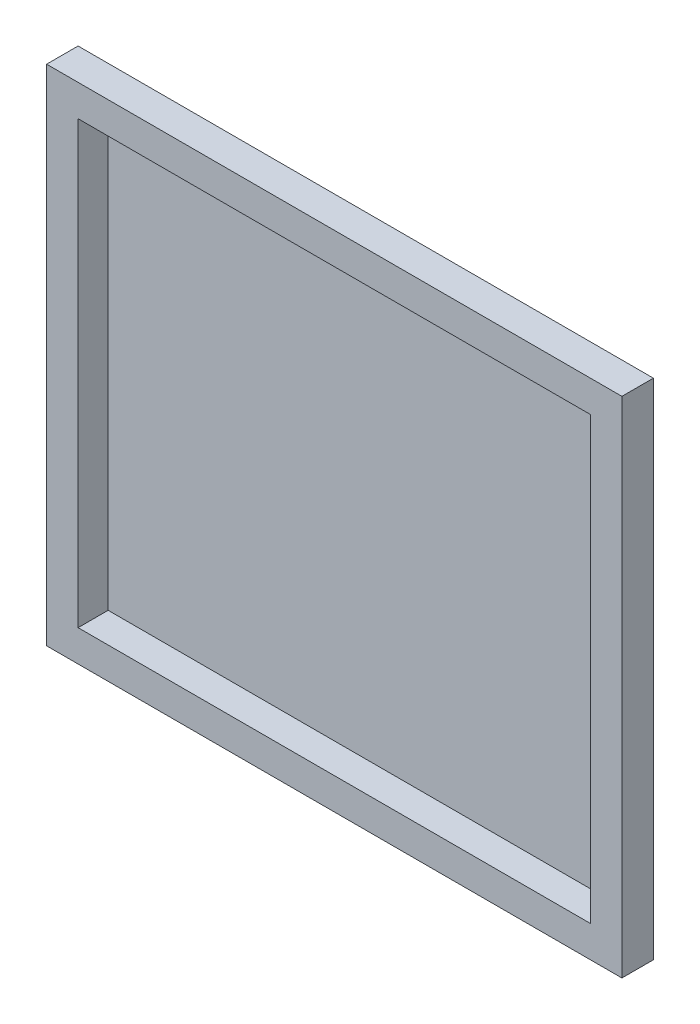
SolidWorks part; units mm, degrees
material "3.0205 (EN-AW 1200)"
ref_plane "정면" through (0, 0, 0) normal (0, 0, 1) x (1, 0, 0)
ref_plane "윗면" through (0, 0, 0) normal (0, 1, 0) x (1, 0, 0)
ref_plane "우측면" through (0, 0, 0) normal (1, 0, 0) x (0, 0, -1)
sketch "스케치1" plane through (0, 0, 0) normal (0, 0, 1) x (1, 0, 0)
  line L1 (0, 0) -> (402, 0)
  line L2 (0, 0) -> (0, -352)
  line L3 (0, -352) -> (402, -352)
  line L4 (402, 0) -> (402, -352)
  line L5 (22, -22) -> (380, -22)
  line L6 (22, -22) -> (22, -330)
  line L7 (22, -330) -> (380, -330)
  line L8 (380, -22) -> (380, -330)
  dimension "D1" = 352
  dimension "D2" = 402
  dimension "D3" = 22
  dimension "D4" = 22
  dimension "D5" = 22
  dimension "D6" = 22
extrude "보스-돌출2" add sketch "스케치1" along normal blind 1 from vertex contours L8 L5 L6 L7 region at (201, -176, 0) starting at point (380, -330, 0)
extrude "보스-돌출3" add sketch "스케치1<6>" along normal blind 22
sketch "스케치1<6>" plane through (0, 0, 0) normal (0, 0, 1) x (1, 0, 0) same geometry as "스케치1"
